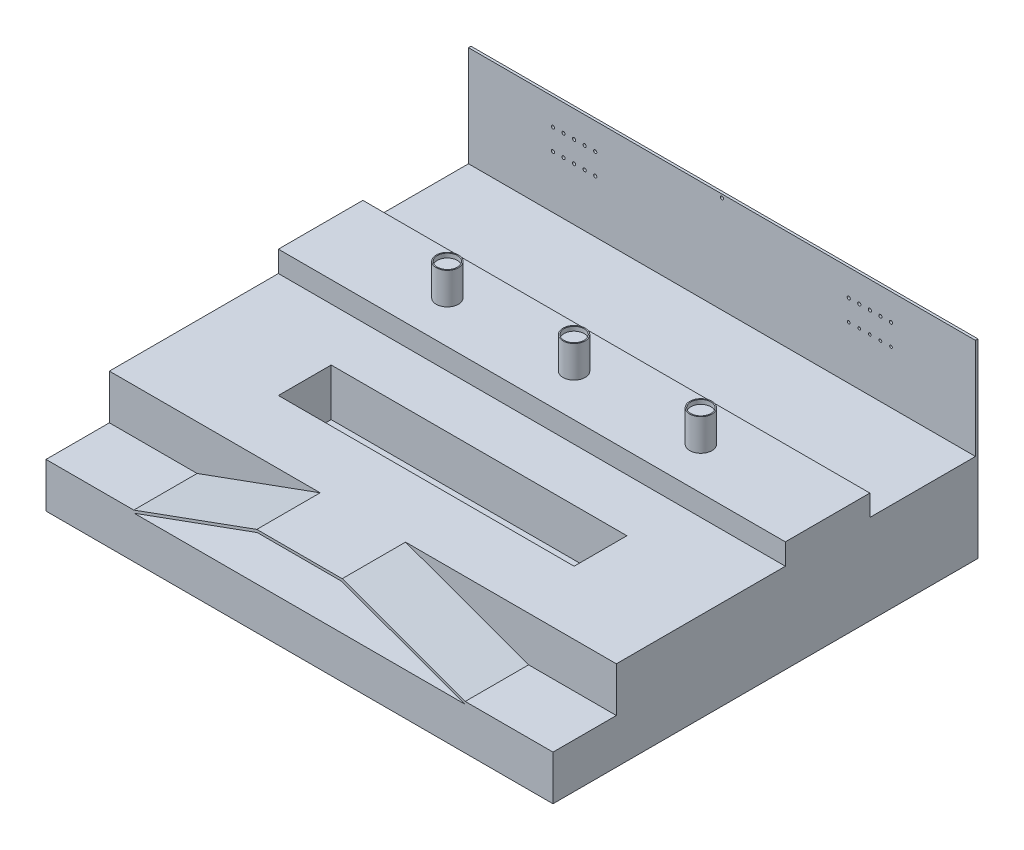
SolidWorks part; units mm, degrees
ref_plane "前视基准面" through (0, 0, 0) normal (0, 0, 1) x (1, 0, 0)
ref_plane "上视基准面" through (0, 0, 0) normal (0, 1, 0) x (1, 0, 0)
ref_plane "右视基准面" through (0, 0, 0) normal (1, 0, 0) x (0, 0, -1)
sketch "草图1" plane through (0, 0, 0) normal (0, 0, 1) x (1, 0, 0)
  line L0 (-200, 0) -> (200, 0)
  line L1 (-200, 0) -> (-782.4652, -212)
  line L2 (200, 0) -> (782.4652, -212)
  line L3 (-1200, -200) -> (-784.5811, -200)
  line L4 (202.1159, 12) -> (784.5811, -200)
  line L5 (-202.1159, 12) -> (202.1159, 12)
  line L6 (-202.1159, 12) -> (-784.5811, -200)
  line L7 (-202.1159, 12) -> (-753.5997, -188.7237) construction
  line L8 (-1200, -212) -> (-782.4652, -212)
  line L9 (-200, 0) -> (-749.4955, -200) construction
  line L10 (202.1159, 12) -> (787.1681, -200.9416) construction
  line L11 (200, 0) -> (783.0639, -212.2179) construction
  line L12 (784.5811, -200) -> (1200, -200)
  line L13 (-1200, -200) -> (1200, -200) construction
  line L14 (782.4652, -212) -> (1200, -212)
  line L15 (-1200, -212) -> (1200, -212) construction
  line L16 (-1200, -200) -> (-1200, -212)
  line L17 (1200, -200) -> (1200, -212)
  point P17 (-1200, -206)
  dimension "D1" = 160
  dimension "D2" = 160
  dimension "D3" = 200
  dimension "D6" = 12
  dimension "D7" = 2400
  dimension "D4" = 12
  dimension "D5" = 12
extrude "凸台-拉伸1" add sketch "草图1" along normal blind 300
sketch "草图2" plane through (0, 0, 0) normal (0, 0, -1) x (-1, 0, 0)
  line L0 (-1200, -212) -> (-1200, 12)
  line L1 (1200, -212) -> (1200, 12)
  line L2 (-1200, -212) -> (1200, -212)
  line L4 (-1200, 12) -> (1200, 12)
  dimension "D1" = 224
extrude "凸台-拉伸2" add sketch "草图2" along normal blind 800
sketch "草图4" plane through (0, 12, 0) normal (0, 1, 0) x (1, 0, 0)
  line L0 (-1200, 800) -> (1200, 800) construction
  line L1 (-700, 300) -> (700, 300)
  line L2 (-700, 300) -> (-700, 550)
  line L3 (-700, 550) -> (700, 550)
  line L4 (700, 300) -> (700, 550)
  line L5 (-1200, 800) -> (-1200, 0) construction
  line L6 (1200, 800) -> (1200, 0) construction
  dimension "D1" = 250
  dimension "D2" = 250
  dimension "D3" = 500
  dimension "D4" = 500
extrude "切除-拉伸1" cut sketch "草图4" against normal through all
sketch "草图7" plane through (0, 0, -800) normal (0, 0, -1) x (-1, 0, 0)
  line L0 (-1200, -212) -> (-1200, 112)
  line L1 (-1200, 112) -> (1200, 112)
  line L2 (1200, 112) -> (1200, -212)
  line L3 (1200, -212) -> (-1200, -212)
  line L4 (1200, 12) -> (-1200, 12) construction
  dimension "D1" = 100
extrude "凸台-拉伸3" add sketch "草图7" along normal blind 400
sketch "草图8" plane through (0, 112, 0) normal (0, 1, 0) x (1, 0, 0)
  line L1 (-1200, 800) -> (1200, 800) construction
  circle A0 centre (0, 1000) radius 75
  dimension "D1" = 200
extrude "凸台-拉伸4" [suppressed] add sketch "草图8" along normal blind 150
sketch "草图9" plane through (0, 0, -1200) normal (0, 0, -1) x (-1, 0, 0)
  line L0 (1200, -212) -> (1200, 112) construction
  line L1 (-1200, -212) -> (1200, -212)
  line L2 (-1200, -212) -> (-1200, 12)
  line L3 (-1200, 12) -> (1200, 12)
  line L4 (1200, -212) -> (1200, 12)
  line L5 (1200, 112) -> (-1200, 112) construction
  dimension "D1" = 100
extrude "凸台-拉伸5" add sketch "草图9" along normal blind 500
sketch "草图10" plane through (0, 0, -1700) normal (0, 0, -1) x (-1, 0, 0)
  line L0 (-1200, 488) -> (1200, 488)
  line L1 (-1200, -212) -> (1200, -212)
  line L5 (-1200, 488) -> (-1200, -212)
  line L6 (1200, 488) -> (1200, -212)
  line L7 (1200, 12) -> (-1200, 12) construction
  dimension "D1" = 700
  dimension "D2" = 224
extrude "凸台-拉伸6" add sketch "草图10" along normal blind 12
sketch "草图11" plane through (0, 0, -1700) normal (0, 0, 1) x (1, 0, 0)
  line L0 (-1200, 12) -> (-1200, 488) construction
  line L1 (-1200, 488) -> (1200, 488) construction
  line L2 (1200, 488) -> (1200, 12) construction
  circle A0 centre (-600, 463) radius 25
  circle A1 centre (600, 463) radius 25
  dimension "D1" = 600
  dimension "D2" = 25
  dimension "D3" = 600
  dimension "D4" = 25
extrude "凸台-拉伸7" [suppressed] add sketch "草图11" along normal blind 20
sketch "草图12" plane through (0, -212, 0) normal (0, -1, 0) x (1, 0, 0)
  line L1 (-1200, 300) -> (1200, 300)
  line L2 (-1200, 300) -> (-1200, -1712)
  line L3 (-1200, -1712) -> (1200, -1712)
  line L4 (1200, 300) -> (1200, -1712)
extrude "凸台-拉伸8" add sketch "草图12" along normal blind 200
sketch "草图13" plane through (0, 112, 0) normal (0, 1, 0) x (1, 0, 0)
  line L0 (-1200, 1200) -> (-1200, 800) construction
  line L1 (1200, 1200) -> (1200, 800) construction
  line L2 (-1200, 1200) -> (1200, 1200) construction
  line L3 (-1200, 1200) -> (1200, 1200) construction
  circle A0 centre (-600, 1000) radius 52.5
  circle A1 centre (600, 1000) radius 52.5
  circle A2 centre (0, 1000) radius 52.5
  dimension "D1" = 600
  dimension "D2" = 600
  dimension "D3" = 600
  dimension "D4" = 200
  dimension "D5" = 200
  dimension "D6" = 200
extrude "凸台-拉伸9" add sketch "草图13" along normal blind 150
sketch "草图14" plane through (0, 0, -1700) normal (0, 0, 1) x (1, 0, 0)
  line L0 (-1200, 12) -> (-1200, 488) construction
  line L1 (1200, 488) -> (1200, 12) construction
  line L3 (-1200, 12) -> (1200, 12) construction
  circle A0 centre (-800, 262) radius 7.5
  circle A1 centre (800, 362) radius 7.5
  circle A2 centre (-750, 262) radius 7.5
  circle A3 centre (-700, 262) radius 7.5
  circle A4 centre (-650, 262) radius 7.5
  circle A5 centre (-600, 262) radius 7.5
  circle A6 centre (750, 362) radius 7.5
  circle A7 centre (700, 362) radius 7.5
  circle A8 centre (650, 362) radius 7.5
  circle A9 centre (600, 362) radius 7.5
  circle A10 centre (0, 472) radius 7.5
  circle A11 centre (-800, 362) radius 7.5
  circle A12 centre (-750, 362) radius 7.5
  circle A13 centre (-700, 362) radius 7.5
  circle A14 centre (-650, 362) radius 7.5
  circle A15 centre (-600, 362) radius 7.5
  circle A16 centre (800, 262) radius 6.5
  circle A17 centre (750, 262) radius 6.5
  circle A18 centre (700, 262) radius 6.5
  circle A19 centre (650, 262) radius 6.5
  circle A20 centre (600, 262) radius 6.5
  dimension "D1" = 400
  dimension "D2" = 400
  dimension "D3" = 250
  dimension "D7" = 460
  dimension "D8" = 100
  dimension "D9" = 5
  dimension "D10" = 100
  dimension "D4" = 350
  dimension "D5" = 5
  dimension "D6" = 5
extrude "切除-拉伸2" cut sketch "草图14" against normal through all
sketch "草图16" plane through (0, 262, 0) normal (0, 1, 0) x (1, 0, 0)
  circle A0 centre (-600, 1000) radius 47.5
  circle A1 centre (0, 1000) radius 47.5
  circle A2 centre (600, 1000) radius 47.5
extrude "切除-拉伸3" cut sketch "草图16" against normal blind 20
